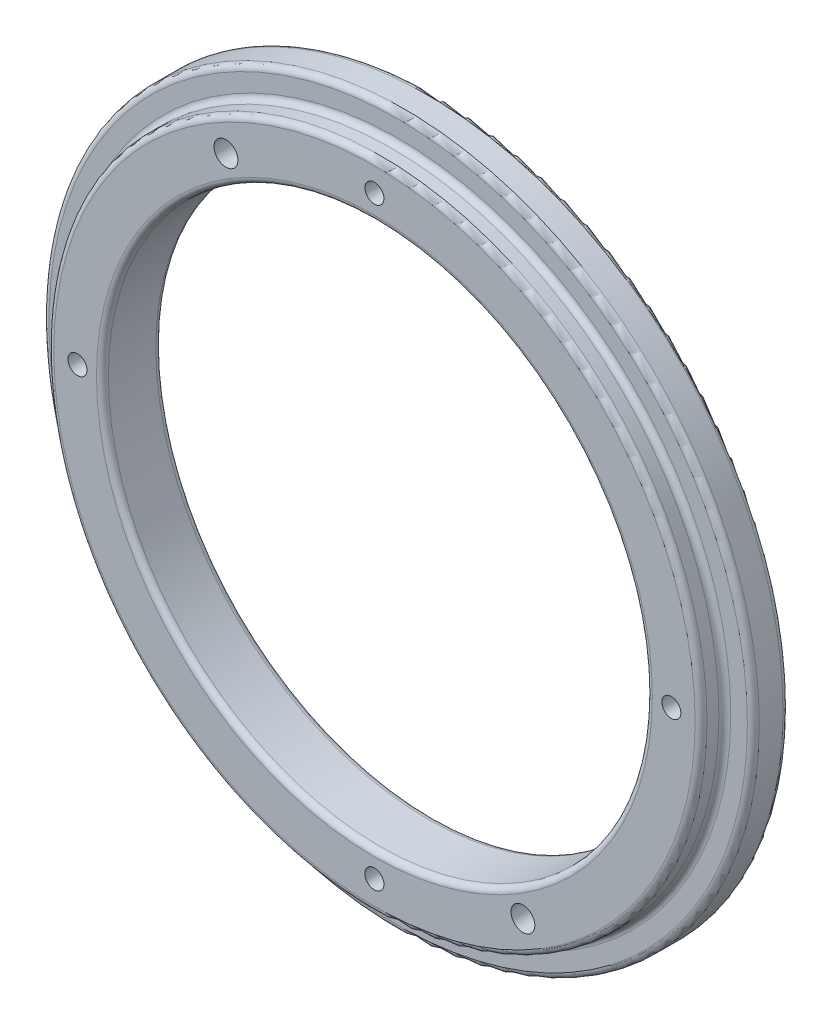
SolidWorks part; units mm, degrees
material "6061 Alloy"
ref_plane "Front Plane" through (0, 0, 0) normal (0, 0, 1) x (1, 0, 0)
ref_plane "Top Plane" through (0, 0, 0) normal (0, 1, 0) x (1, 0, 0)
ref_plane "Right Plane" through (0, 0, 0) normal (1, 0, 0) x (0, 0, -1)
sketch "Bulkhead Lid Profile" plane through (0, 0, 0) normal (0, 0, 1) x (1, 0, 0)
  circle A0 centre (0, 0) radius 75.946
  circle A1 centre (0, 0) radius 58.166
  dimension "D1" = 151.892
  dimension "D2" = 116.332
extrude "Bulkhead Lid Body" add sketch "Bulkhead Lid Profile" along normal blind 7.62
sketch "Lip Profile" plane through (0, 0, 7.62) normal (0, 0, 1) x (1, 0, 0)
  circle A0 centre (0, 0) radius 69.85
  circle A2 centre (0, 0) radius 58.166 construction
  circle A3 centre (0, 0) radius 58.166
  dimension "D1" = 139.7
extrude "Bulkhead Lid Lip" add sketch "Lip Profile" along normal blind 5.08
sketch "Screw Hole Profile" plane through (0, 0, 0) normal (0, 0, -1) x (-1, 0, 0)
  line L0 (0, 0) -> (0, 63.5) construction
  circle A0 centre (0, 63.5) radius 2.032
  circle A1 centre (63.5, 0) radius 2.032
  circle A2 centre (0, -63.5) radius 2.032
  circle A3 centre (-63.5, 0) radius 2.032
  point P14 (0, 0)
  dimension "D1" = 63.5
  dimension "D2" = 4.064
  dimension "D3" = 4
extrude "Bulkhead Screw Holes" cut sketch "Screw Hole Profile" against normal through all
fillet "Fillet1" radius 1.27 6 edges at (58.166, 0, 12.7) (58.166, 0, 0) (69.85, 0, 7.62) (69.85, 0, 12.7) (75.946, 0, 7.62) (75.946, 0, 0)
sketch "Threaded Rod Profile" plane through (0, 0, 0) normal (0, 0, -1) x (-1, 0, 0)
  line L0 (-37.973, -65.7712) -> (37.973, 65.7712) construction
  line L1 (0, 0) -> (-75.946, 0) construction
  circle A0 centre (0, 0) radius 75.946 construction
  circle A1 centre (-31.75, -54.9926) radius 2.5527
  circle A2 centre (31.75, 54.9926) radius 2.5527
  point P4 (0, 0)
  dimension "D2" = 63.5
  dimension "D4" = 5.1054
  dimension "D1" = 120
  dimension "D3" = 63.5
extrude "Threaded Rod Holes" cut sketch "Threaded Rod Profile" against normal through all
